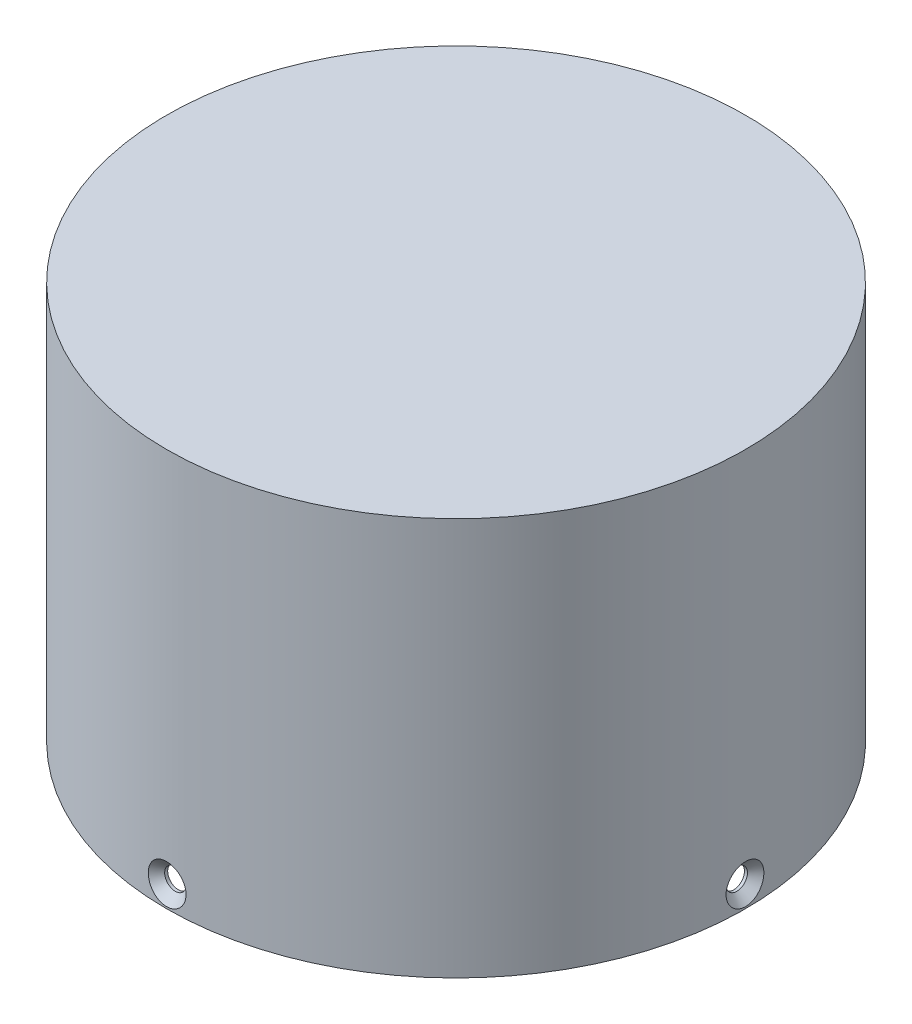
SolidWorks part; units mm, degrees
ref_plane "Front Plane" through (0, 0, 0) normal (0, 0, 1) x (1, 0, 0)
ref_plane "Top Plane" through (0, 0, 0) normal (0, 1, 0) x (1, 0, 0)
ref_plane "Right Plane" through (0, 0, 0) normal (1, 0, 0) x (0, 0, -1)
sketch "Sketch3" plane through (0, 0, 0) normal (0, 1, 0) x (1, 0, 0)
  circle A0 centre (0, 0) radius 23
  dimension "D1" = 46
extrude "Boss-Extrude3" add sketch "Sketch3" along normal blind 31.6
sketch "Sketch4" plane through (0, 0, 0) normal (0, -1, 0) x (1, 0, 0)
  circle A0 centre (0, 0) radius 22.075
  dimension "D1" = 44.15
extrude "Cut-Extrude1" cut sketch "Sketch4" against normal blind 30.6
hole_wizard "CSK for M2 Flat Head Machine Screw2" positions "3DSketch1" profile "Sketch5" countersink size "M2" standard "ANSI Metric" end condition up to next
sketch3d "3DSketch1"
  point P0 (23, 1.7, 0)
sketch "Sketch5" plane through (23, 1.7, 0) normal (0, 1, 0) x (0, 0, -1)
  line L0 (0, 0) -> (0, 0.925)
  line L1 (0, 0.925) -> (0.85, 0.925)
  line L2 (0.85, 0.925) -> (0.85, 0.7)
  line L3 (0.85, 0.7) -> (1.55, 0)
  line L5 (1.55, 0) -> (0, 0)
  line L6 (-0.85, 0.7) -> (-1.55, 0) construction
  line L11 (0, -6.35) -> (0, 107.95) construction
  dimension "Thru Hole Dia." = 1.7
  dimension "Thru Hole Depth" = 0.925
  dimension "Near C'Sink Dia." = 3.1
  dimension "Near C'Sink Angle" = 90
ref_axis "Axis1" through (0, 30.6, 0) along (0, -1, 0)
pattern_circular "CirPattern1" count 4 over 360 about axis through (0, 30.6, 0) along (0, -1, 0) of "CSK for M2 Flat Head Machine Screw2"
